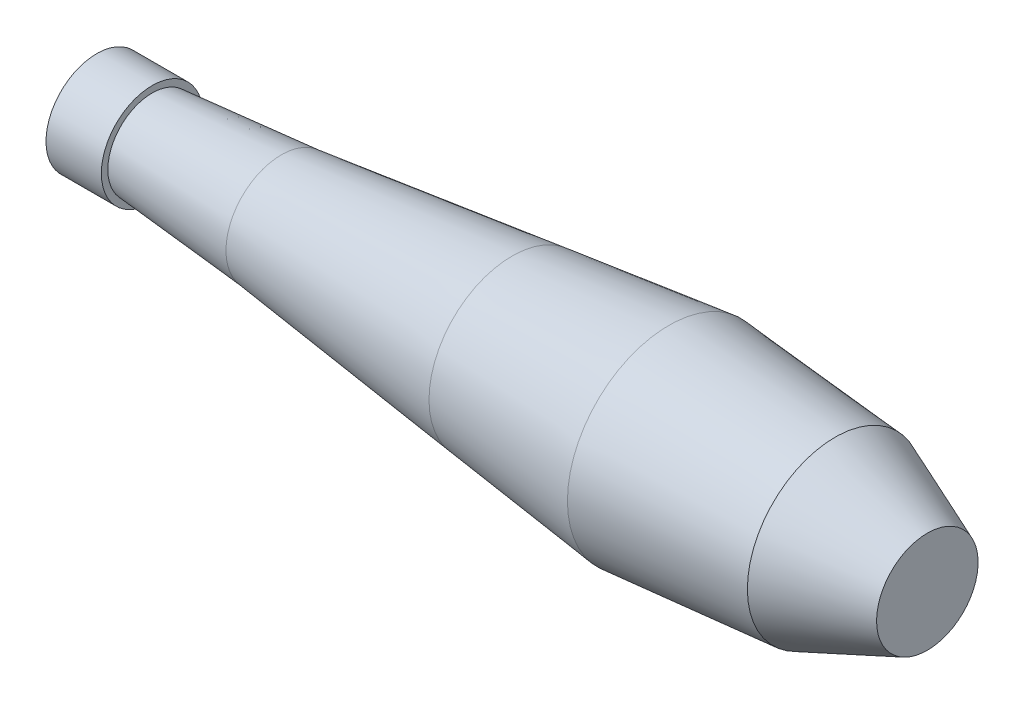
SolidWorks part; units mm, degrees
material "Oak"
ref_plane "Front Plane" through (0, 0, 0) normal (0, 0, 1) x (1, 0, 0)
ref_plane "Top Plane" through (0, 0, 0) normal (0, 1, 0) x (1, 0, 0)
ref_plane "Right Plane" through (0, 0, 0) normal (1, 0, 0) x (0, 0, -1)
sketch "Sketch1" plane through (0, 0, 0) normal (0, 0, 1) x (1, 0, 0)
  line L0 (0, 0) -> (90, 0) construction
  line L1 (0, 0) -> (0, 5.5)
  line L2 (0, 5.5) -> (6, 5.5)
  line L3 (6, 5.5) -> (6, 4.8)
  line L4 (6, 4.8) -> (20, 6)
  line L5 (20, 6) -> (45, 9)
  line L6 (45, 9) -> (62, 11)
  line L7 (62, 11) -> (80, 9.5)
  line L8 (80, 9.5) -> (90, 5.5)
  line L9 (90, 5.5) -> (90, 0)
  line L10 (90, 0) -> (0, 0)
  dimension "D1" = 90
  dimension "D2" = 5.5
  dimension "D3" = 6
  dimension "D4" = 0.7
  dimension "D5" = 5.5
  dimension "D6" = 14
  dimension "D7" = 1.2
  dimension "D8" = 25
  dimension "D9" = 3
  dimension "D10" = 17
  dimension "D11" = 2
  dimension "D12" = 18
  dimension "D13" = 1.5
revolve "Revolve1" add sketch "Sketch1" angle 360 about L0
ref_axis "Axis1" through (-4.5, 0, 0) along (1, 0, 0)
